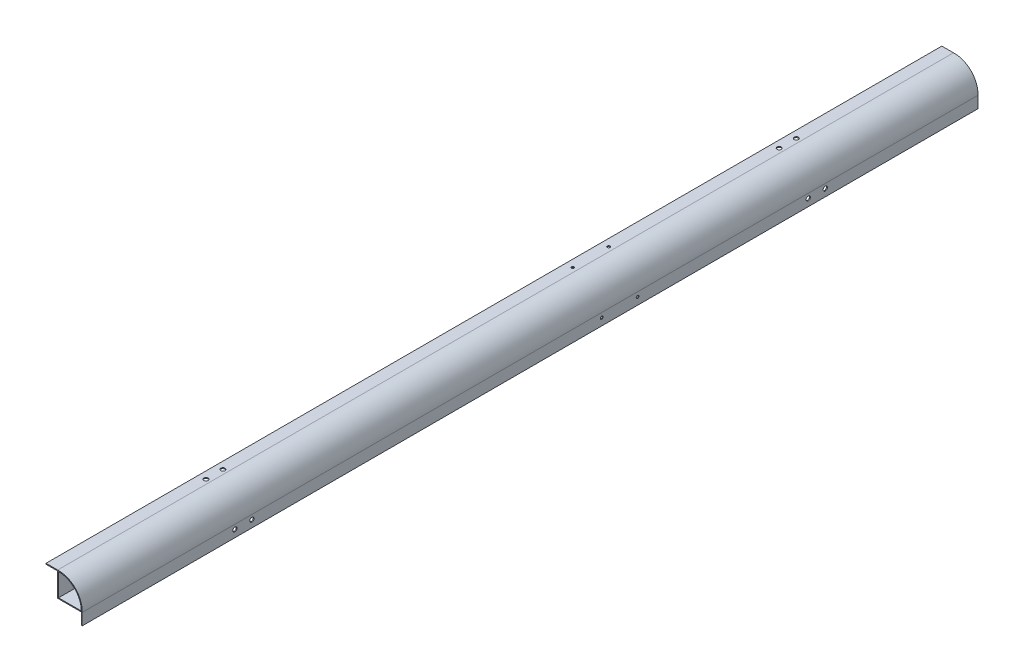
SolidWorks part; units mm, degrees
ref_plane "Alzado" through (0, 0, 0) normal (0, 0, 1) x (1, 0, 0)
ref_plane "Planta" through (0, 0, 0) normal (0, 1, 0) x (1, 0, 0)
ref_plane "Vista lateral" through (0, 0, 0) normal (1, 0, 0) x (0, 0, -1)
sketch "Croquis1" plane through (0, 0, 0) normal (0, 0, 1) x (1, 0, 0)
  line L0 (-13.7, -13.7) -> (13.6811, -13.7)
  line L1 (-12.7, -12.7) -> (12.7, -12.7)
  line L2 (-12.7, -12.7) -> (-12.7, 12.7)
  line L5 (0, 16.5842) -> (0, -23.118) construction
  line L6 (-13.7, -13.7) -> (-13.7, 13.6811)
  line L8 (-18.0998, 0) -> (17.5647, 0) construction
  line L9 (13.6811, -13.7) -> (12.6811, -13.7)
  line L10 (13.6811, -13.7) -> (13.6811, -26.7)
  line L11 (13.6811, -26.7) -> (12.6811, -26.7)
  line L12 (12.6811, -13.7) -> (12.6811, -26.7)
  line L13 (-13.7, 13.6811) -> (-26.7, 13.6811)
  line L14 (-13.7, 13.6811) -> (-13.7, 12.6811)
  line L15 (-13.7, 12.6811) -> (-26.7, 12.6811)
  line L16 (-26.7, 13.6811) -> (-26.7, 12.6811)
  arc A0 (-12.7, 12.7) -> (12.7, -12.7) centre (-12.7, -12.7) cw
  arc A1 (-13.7, 13.6811) -> (13.6811, -13.7) centre (-12.7, -12.7) cw
  point P0 (0, 0)
  point P12 (-12.7, 0)
  point P13 (0, -12.7)
  dimension "D3" = 25.4
  dimension "D1" = 25.4
  dimension "D2" = 25.4
  dimension "D5" = 1
  dimension "D6" = 13
  dimension "D7" = 1
  dimension "D8" = 13
  dimension "D4" = 1
extrude "Saliente-Extruir1" add sketch "Croquis1" along normal mid plane 1000 contours A1 L6 L0 L2 A0 L1 | L13 L16 L15 L6 | L0 L12 L11 L10 region at (-13.3125, -0.5095, 0) region at (13.1811, -20.2, 0) region at (-20.2, 13.1811, 0)
ref_plane "Plano1" through (-12.7, -12.7, 500) normal (0, 1, 0) x (1, 0, 0)
sketch "Croquis2" plane through (13.6811, 0, 0) normal (1, 0, 0) x (0, 0, -1)
  line L0 (0, 93.7538) -> (0, -74.3435) construction
  line L1 (560.0844, 0) -> (-573.6748, 0) construction
  line L2 (320, 46.1161) -> (320, -56.1874) construction
  line L3 (100, 46.1161) -> (100, -56.1874) construction
  line L4 (-500, -26.7) -> (500, -26.7) construction
  line L5 (-320, 46.1161) -> (-320, -56.1874) construction
  line L6 (-500, -13.7) -> (500, -13.7) construction
  circle A0 centre (310.5, -18.7) radius 2.3813
  circle A1 centre (329.5, -18.7) radius 2.3813
  circle A2 centre (310.5, -18.7) radius 2.3813
  circle A3 centre (329.5, -18.7) radius 2.3813
  circle A4 centre (310.5, -18.7) radius 2.3813
  circle A5 centre (329.5, -18.7) radius 2.3813
  circle A6 centre (310.5, -18.7) radius 2.3813
  circle A7 centre (329.5, -18.7) radius 2.3813
  circle A8 centre (-329.5, -18.7) radius 2.3813
  circle A9 centre (-310.5, -18.7) radius 2.3813
  circle A10 centre (-329.5, -18.7) radius 2.3813
  circle A11 centre (-310.5, -18.7) radius 2.3813
  circle A12 centre (-329.5, -18.7) radius 2.3813
  circle A13 centre (-310.5, -18.7) radius 2.3813
  circle A14 centre (-329.5, -18.7) radius 2.3813
  circle A15 centre (-310.5, -18.7) radius 2.3813
  circle A16 centre (120, -18.7) radius 1.5
  circle A17 centre (80, -18.7) radius 1.5
  dimension "D2" = 4.7625
  dimension "D7" = 3
  dimension "D1" = 9.5
  dimension "D3" = 320
  dimension "D4" = 8
  dimension "D5" = 100
  dimension "D6" = 20
  dimension "D8" = 5
extrude "Cortar-Extruir1" cut sketch "Croquis2" against normal blind 10 contours A1 | A0 | A15 | A14 | A17 | A16
sketch "Croquis3" plane through (0, 13.6811, 0) normal (0, 1, 0) x (1, 0, 0)
  line L0 (-69.3307, 320) -> (48.8112, 320) construction
  line L1 (-26.7, -500) -> (-26.7, 500) construction
  line L2 (-105.8003, 100) -> (67.0517, 100) construction
  line L3 (331.1987, 0) -> (-269.3715, 0) construction
  line L4 (-13.7, -500) -> (-13.7, 500) construction
  circle A0 centre (-18.7, 329.5) radius 2.3813
  circle A1 centre (-18.7, 310.5) radius 2.3813
  circle A2 centre (-18.7, -310.5) radius 2.3813
  circle A3 centre (-18.7, -329.5) radius 2.3813
  circle A4 centre (-18.7, 120) radius 1.5
  circle A5 centre (-18.7, 80) radius 1.5
  dimension "D1" = 4.7625
  dimension "D7" = 3
  dimension "D2" = 9.5
  dimension "D3" = 8
  dimension "D4" = 320
  dimension "D5" = 100
  dimension "D6" = 20
  dimension "D8" = 5
extrude "Cortar-Extruir2" cut sketch "Croquis3" against normal blind 10
